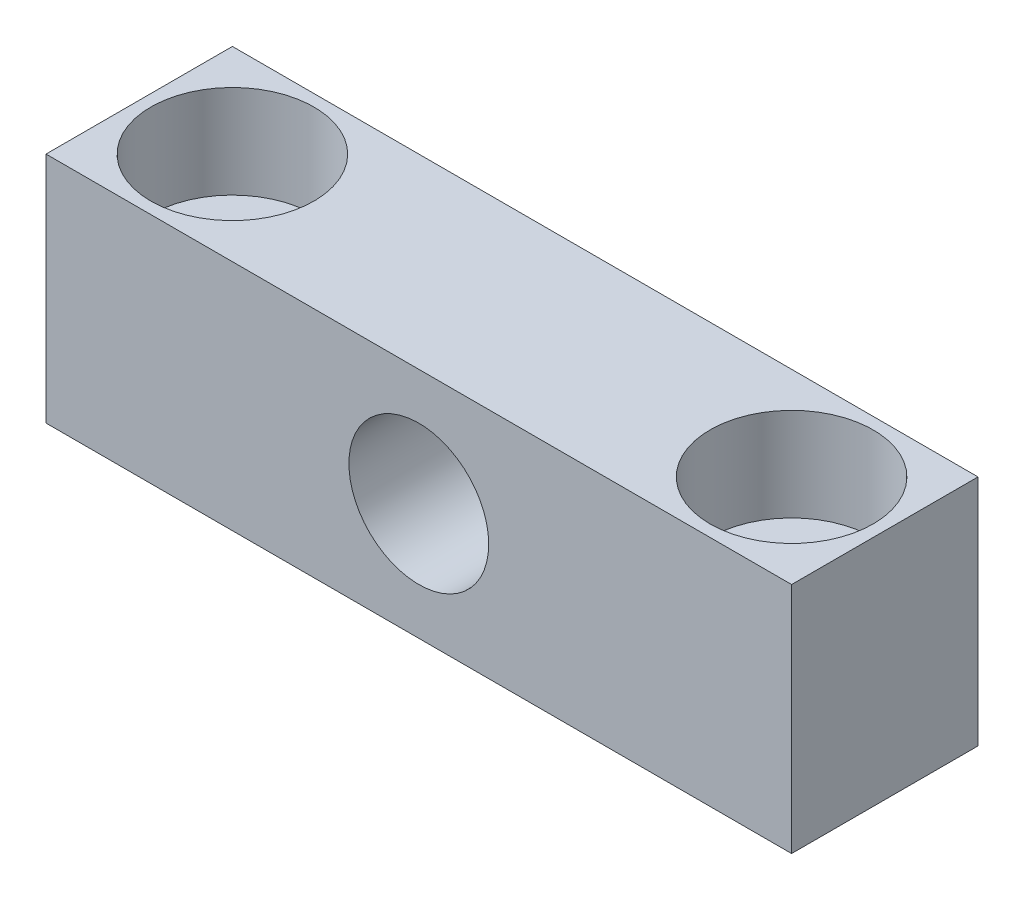
SolidWorks part; units mm, degrees
ref_plane "Front Plane" through (0, 0, 0) normal (0, 0, 1) x (1, 0, 0)
ref_plane "Top Plane" through (0, 0, 0) normal (0, 1, 0) x (1, 0, 0)
ref_plane "Right Plane" through (0, 0, 0) normal (1, 0, 0) x (0, 0, -1)
sketch "Sketch1" plane through (0, 0, 0) normal (0, 1, 0) x (1, 0, 0)
  line L0 (-25.4, 6.35) -> (25.4, -6.35) construction
  line L1 (-25.4, 6.35) -> (25.4, 6.35)
  line L2 (-25.4, 6.35) -> (-25.4, -6.35)
  line L3 (-25.4, -6.35) -> (25.4, -6.35)
  line L4 (25.4, 6.35) -> (25.4, -6.35)
  dimension "D1" = 12.7
  dimension "D2" = 50.8
extrude "Extrude1" add sketch "Sketch1" along normal blind 15.875
sketch "Sketch3" plane through (0, 0, 6.35) normal (0, 0, 1) x (1, 0, 0)
  line L0 (0, 15.875) -> (0, 0) construction
  line L1 (-25.4, 15.875) -> (25.4, 15.875) construction
  line L2 (-25.4, 0) -> (25.4, 0) construction
  circle A0 centre (0, 7.9375) radius 4.7625
  dimension "D1" = 9.525
extrude "Cut-Extrude2" cut sketch "Sketch3" against normal through all
hole_wizard "CBORE for 1/4 Socket Head Cap Screw1" positions "Sketch5" profile "Sketch4" counterbore size "1/4" standard "Ansi Inch" end condition through all
sketch "Sketch5" plane through (0, 15.875, 0) normal (0, 1, 0) x (-1, 0, 0)
  line L1 (25.4, 0) -> (-25.4, 0) construction
  line L2 (25.4, -6.35) -> (25.4, 6.35) construction
  line L3 (-25.4, 6.35) -> (-25.4, -6.35) construction
  line L4 (0, -6.35) -> (0, 6.35) construction
  line L5 (-25.4, -6.35) -> (25.4, -6.35) construction
  line L6 (25.4, 6.35) -> (-25.4, 6.35) construction
  point P0 (-19.05, 0)
  point P1 (19.05, 0)
  dimension "D1" = 38.1
sketch "Sketch4" plane through (19.05, 15.875, 0) normal (1, 0, 0) x (0, 0, 1)
  line L0 (0, 0) -> (0, 15.875)
  line L1 (0, 15.875) -> (3.3782, 15.875)
  line L3 (3.3782, 15.875) -> (3.3782, 6.35)
  line L4 (3.3782, 6.35) -> (5.5562, 6.35)
  line L5 (5.5562, 6.35) -> (5.5562, 0)
  line L7 (5.5562, 0) -> (0, 0)
  line L11 (0, -6.35) -> (0, 107.95) construction
  dimension "Thru Hole Dia." = 6.7564
  dimension "Thru Hole Depth" = 15.875
  dimension "C'Bore Dia." = 11.1125
  dimension "C'Bore Depth" = 6.35
